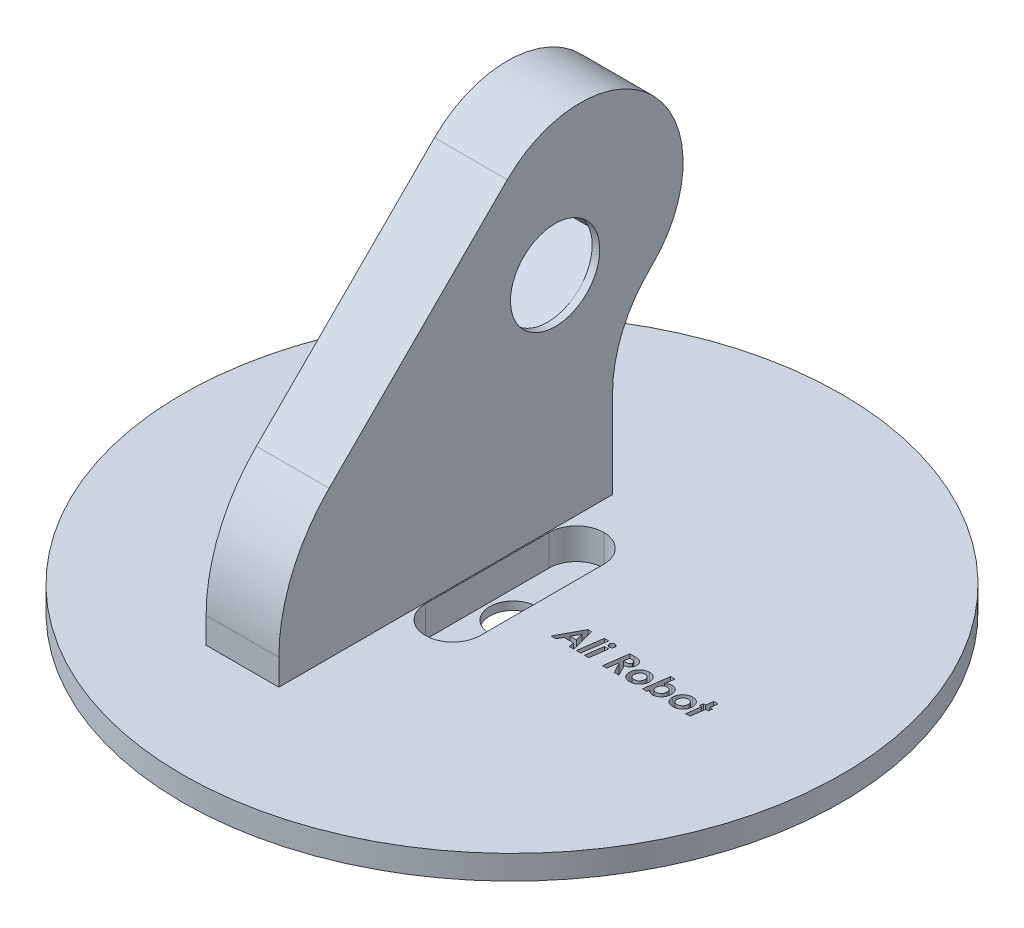
SolidWorks part; units mm, degrees
ref_plane "Front Plane" through (0, 0, 0) normal (0, 0, 1) x (1, 0, 0)
ref_plane "Top Plane" through (0, 0, 0) normal (0, 1, 0) x (1, 0, 0)
ref_plane "Right Plane" through (0, 0, 0) normal (1, 0, 0) x (0, 0, -1)
sketch "Sketch2" plane through (0, 0, 0) normal (0, 1, 0) x (1, 0, 0)
  circle A0 centre (0, 0) radius 48
  dimension "D1" = 96
extrude "Boss-Extrude1" add sketch "Sketch2" along normal blind 3.5
ref_plane "Plane1" through (-4, 0, 0) normal (1, 0, 0) x (0, 0, -1)
sketch "Sketch7" plane through (-4, 0, 0) normal (1, 0, 0) x (0, 0, -1)
  line L0 (18.6521, 16.3561) -> (18.6521, 3.5)
  line L5 (48, 3.5) -> (-48, 3.5) construction
  line L6 (-22.6311, 24.9401) -> (3.3119, 50.8831)
  line L7 (-43.5609, 3.5) -> (18.6521, 3.5)
  line L11 (-29.9535, 3.5) -> (-29.9535, 7.2624)
  arc A4 (24.252, 29.4036) -> (3.3119, 50.8831) centre (13.9185, 40.2765) ccw
  arc A5 (24.252, 29.4036) -> (18.6521, 16.3561) centre (36.6521, 16.3561) ccw
  arc A6 (-22.6311, 24.9401) -> (-29.9535, 7.2624) centre (-4.9535, 7.2624) ccw
  dimension "D1" = 25
  dimension "D4" = 30
  dimension "D3" = 18
  dimension "D5" = 45
extrude "Boss-Extrude2" add sketch "Sketch7" against normal blind 10.6 contours A5 A4 L6 L7 L0 | A4 | A4 | A4 | L6 A6 L7 region at (-4, 25.827, -1.7732)
ref_plane "Plane2" through (-6, 0, 0) normal (1, 0, 0) x (0, 0, -1)
sketch "Sketch31" plane through (-14.6, 10.4618, -5.3595) normal (-1, 0, 0) x (0, 0, 1)
  line L0 (-5.4155, 34.0546) -> (11.7496, 18.7458)
  line L1 (11.7496, 18.7458) -> (3.0968, 9.0438)
  line L2 (3.0968, 9.0438) -> (-14.0683, 24.3526)
  line L3 (-14.0683, 24.3526) -> (-5.4155, 34.0546)
  circle A0 centre (-4.9225, 24.9054) radius 6.5
  dimension "D1" = 6.5
extrude "Cut-Extrude18" cut sketch "Sketch31" against normal through all contours A0
extrude "Cut-Extrude19" cut sketch "Sketch31<3>" against normal blind 9.5 contours L0 L1 L2 L3
sketch "Sketch31<3>" plane through (-14.6, 10.4618, -5.3595) normal (-1, 0, 0) x (0, 0, 1) same geometry as "Sketch31"
sketch "Sketch32" plane through (-14.6, 0, 0) normal (-1, 0, 0) x (0, 0, 1)
  line L0 (6.3901, 29.2076) -> (-2.2627, 19.5056) construction
  circle A0 centre (-17.0806, 41.2645) radius 1
  circle A1 centre (3.9294, 22.6926) radius 1
  arc A3 (-14.6084, 40.2182) -> (-15.5944, 39.1126) centre (-10.282, 35.3672) ccw construction
  dimension "D1" = 2.5
  dimension "D2" = 2.5
extrude "Cut-Extrude20" cut sketch "Sketch32" against normal blind 4.5
sketch "Sketch33" plane through (0, 0, 0) normal (0, -1, 0) x (1, 0, 0)
  circle A0 centre (0, 0) radius 42.5
  dimension "D1" = 85
extrude "Boss-Extrude3" add sketch "Sketch33" along normal blind 2.2
sketch "Sketch34" plane through (-3.9333, 3.5, 15.1139) normal (0, 1, 0) x (1, 0, 0)
  line L1 (0.0806, 2.3531) -> (8.0806, 2.3531)
  line L2 (0.0806, 2.3531) -> (0.0806, 28.3531)
  line L3 (0.0806, 28.3531) -> (8.0806, 28.3531)
  line L4 (8.0806, 2.3531) -> (8.0806, 28.3531)
  dimension "D1" = 26
  dimension "D2" = 8
extrude "Cut-Extrude21" cut sketch "Sketch34" against normal blind 4.5
sketch "Sketch35" plane through (64.9204, 3.5, -6.6124) normal (0, 1, 0) x (1, 0, 0)
  circle A0 centre (-64.8162, -6.541) radius 3.43
  dimension "D1" = 6.86
extrude "Cut-Extrude22" cut sketch "Sketch35" against normal through all
fillet "Fillet1" radius 4 4 edges at (4.1473, 1.25, 12.7608) (-3.8527, 1.25, 12.7608) (4.1473, 1.25, -13.2392) (-3.8527, 1.25, -13.2392)
sketch "Sketch36" plane through (-0.3649, -1, -0.2316) normal (0, 1, 0) x (1, 0, 0)
  circle A0 centre (0.9998, 5.746) radius 1
  circle A1 centre (0.9966, -6.0667) radius 1
  circle A3 centre (0.4691, -0.1602) radius 3.43 construction
  dimension "D1" = 2.5
  dimension "D2" = 2.5
extrude "Cut-Extrude23" cut sketch "Sketch36" against normal blind 4.5
sketch "Sketch38" plane through (0, 3.5, 0) normal (0, 1, 0) x (1, 0, 0)
  text T0 "<b><i>Ali Robot</i></b>"
extrude "Cut-Extrude24" cut sketch "Sketch38" against normal blind 3
